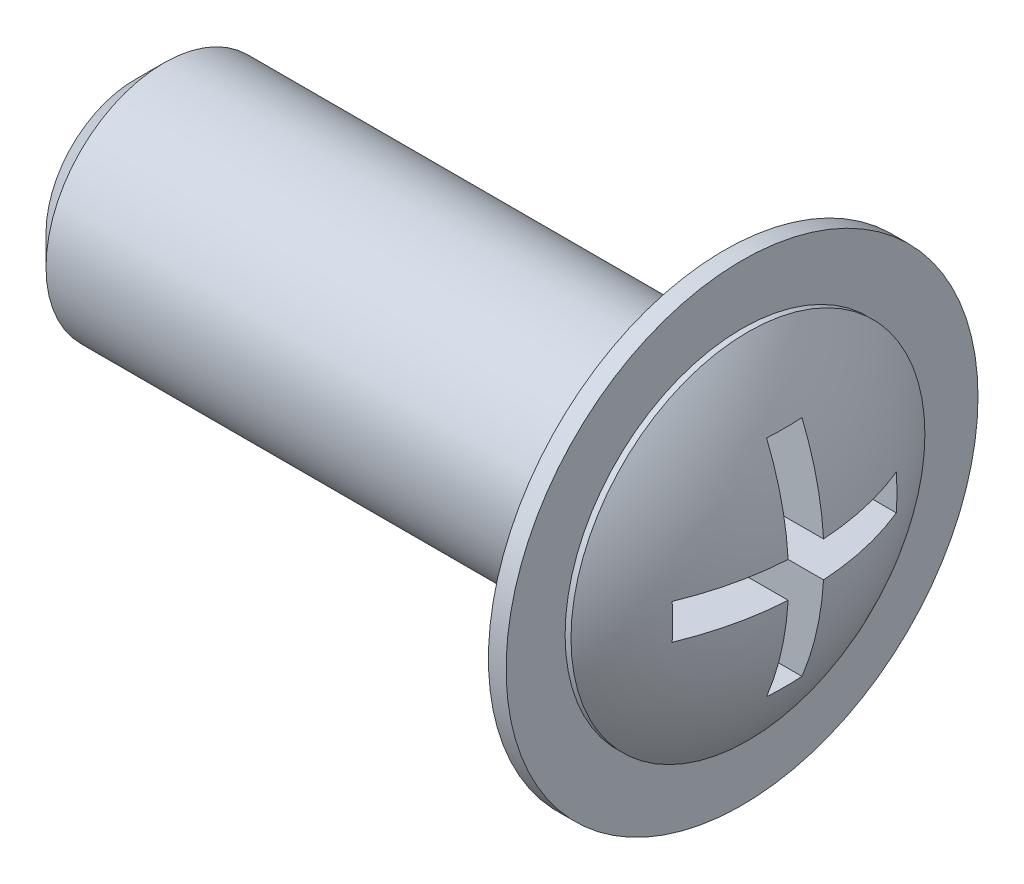
SolidWorks part; units mm, degrees
ref_plane "前视基准面" through (0, 0, 0) normal (0, 0, 1) x (1, 0, 0)
ref_plane "上视基准面" through (0, 0, 0) normal (0, 1, 0) x (1, 0, 0)
ref_plane "右视基准面" through (0, 0, 0) normal (1, 0, 0) x (0, 0, -1)
sketch "草图1" plane through (0, 0, 0) normal (1, 0, 0) x (0, 0, -1)
  circle A0 centre (0, 0) radius 4
  dimension "D1" = 8
extrude "凸台-拉伸1" add sketch "草图1" along normal blind 0.3
sketch "草图2" plane through (0, 0, 0) normal (-1, 0, 0) x (0, 0, 1)
  circle A0 centre (0, 0) radius 2
  dimension "D1" = 4
extrude "凸台-拉伸3" add sketch "草图2" along normal blind 10
sketch "草图5" plane through (0, 0, 0) normal (1, 0, 0) x (0, 0, -1)
  line L0 (0.3, 0.3) -> (1.9, 0.3)
  line L1 (1.9, 0.3) -> (1.9, -0.3)
  line L2 (1.9, -0.3) -> (0.3, -0.3)
  line L3 (0.3, -0.3) -> (0.3, -1.9)
  line L4 (0.3, -1.9) -> (-0.3, -1.9)
  line L5 (-0.3, -1.9) -> (-0.3, -0.3)
  line L6 (-0.3, -0.3) -> (-1.9, -0.3)
  line L7 (-1.9, -0.3) -> (-1.9, 0.3)
  line L8 (-1.9, 0.3) -> (-0.3, 0.3)
  line L9 (-0.3, 0.3) -> (-0.3, 1.9)
  line L10 (-0.3, 1.9) -> (0.3, 1.9)
  line L11 (0.3, 1.9) -> (0.3, 0.3)
  dimension "D1" = 0.6
  dimension "D2" = 0.6
  dimension "D3" = 0.6
  dimension "D4" = 0.6
  dimension "D5" = 0.3
  dimension "D6" = 0.3
  dimension "D7" = 0.3
  dimension "D8" = 0.3
  dimension "D9" = 1.6
  dimension "D10" = 1.6
  dimension "D11" = 1.6
  dimension "D12" = 1.6
sketch "草图6" plane through (0.3, 0, 0) normal (1, 0, 0) x (0, 0, -1)
  circle A0 centre (0, 0) radius 3
  dimension "D1" = 6
extrude "凸台-拉伸4" add sketch "草图6" along normal blind 0.1
dome "圆顶1" faces to dome 1 distance 1 reverse direction no elliptical dome no face at (0.4, 0, -3) parameters "D1"=1
extrude "切除-拉伸2" cut sketch "草图5" along normal blind 3
chamfer "倒角1" distance 0.5 angle 45 1 edges at (-10, 0, 2)
